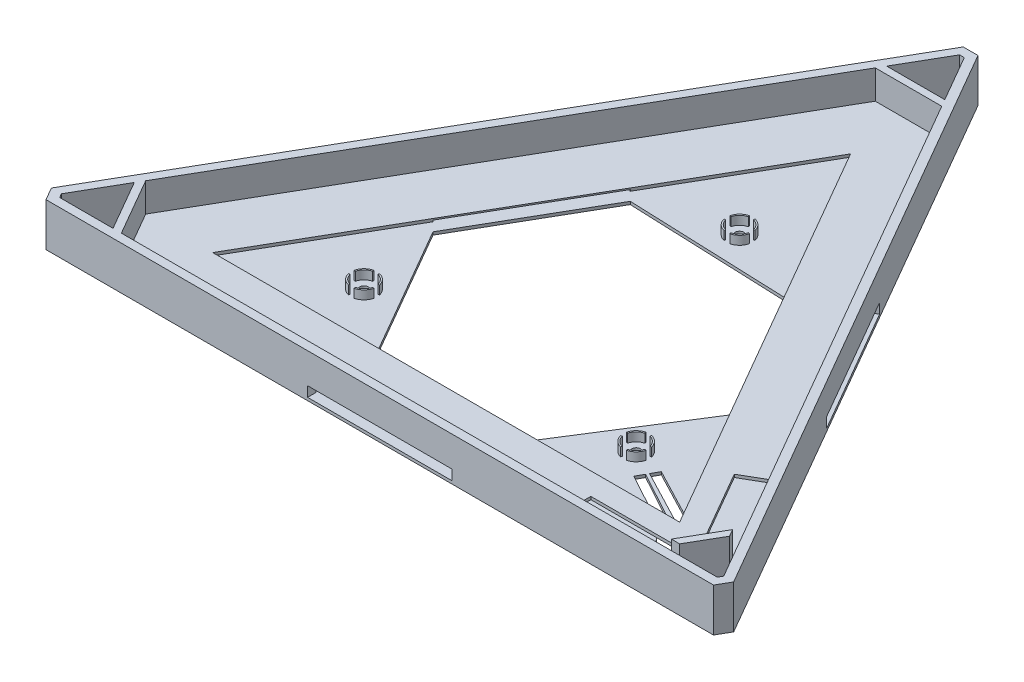
SolidWorks part; units mm, degrees
ref_plane "Front Plane" through (0, 0, 0) normal (0, 0, 1) x (1, 0, 0)
ref_plane "Top Plane" through (0, 0, 0) normal (0, 1, 0) x (1, 0, 0)
ref_plane "Right Plane" through (0, 0, 0) normal (1, 0, 0) x (0, 0, -1)
sketch "Sketch1" plane through (0, 0, 0) normal (0, 1, 0) x (1, 0, 0)
  line L0 (351.2729, 67.6655) -> (468.273, -134.9846)
  line L1 (347.2728, 67.6655) -> (347.2728, 65.1655) construction
  line L2 (409.773, -33.6595) -> (407.6079, -34.9095) construction
  line L3 (468.273, -134.9846) -> (464.2732, -141.9124)
  line L4 (230.2733, -141.9124) -> (464.2732, -141.9124)
  line L5 (230.2733, -141.9124) -> (226.2727, -134.9842)
  line L6 (226.2727, -134.9842) -> (343.2728, 67.6655)
  line L7 (353.4142, 63.9567) -> (351.2491, 62.7067) construction
  line L8 (347.2733, -141.9124) -> (347.2733, -139.4124) construction
  line L9 (231.7167, -139.4124) -> (462.8299, -139.4124)
  line L10 (284.7727, -33.6594) -> (286.9378, -34.9094) construction
  line L11 (344.7161, 65.1655) -> (349.8295, 65.1655)
  line L12 (465.3862, -134.9846) -> (349.8295, 65.1655)
  line L13 (466.2731, -138.4485) -> (464.1081, -137.1985) construction
  line L14 (462.8299, -139.4124) -> (465.3862, -134.9846)
  line L15 (229.1594, -134.9842) -> (344.7161, 65.1655)
  line L16 (229.1594, -134.9842) -> (231.7167, -139.4124)
  line L17 (286.9378, -34.9094) -> (287.3708, -35.1594) construction
  line L18 (230.438, -137.1983) -> (230.871, -136.9483) construction
  line L19 (232.0053, -138.9123) -> (229.7368, -134.9842)
  line L20 (343.2728, 67.6655) -> (351.2729, 67.6655)
  line L21 (345.0048, 64.6655) -> (229.7368, -134.9842)
  line L22 (349.5409, 64.6655) -> (345.0048, 64.6655)
  line L23 (249.0568, -126.4468) -> (246.8918, -127.697) construction
  line L24 (407.6079, -34.9095) -> (407.1749, -35.1595) construction
  line L26 (233.4463, -136.4089) -> (251.9226, -136.4093)
  line L27 (464.8089, -134.9846) -> (462.5412, -138.9123)
  line L28 (462.5412, -138.9123) -> (232.0053, -138.9123)
  line L29 (251.9226, -136.4093) -> (241.8609, -118.9847)
  line L30 (241.8609, -118.9847) -> (232.6236, -134.9842)
  line L31 (232.6236, -134.9842) -> (233.4463, -136.4089)
  line L33 (287.3708, -35.1594) -> (289.5359, -36.4094) construction
  line L34 (254.8093, -136.4089) -> (243.3042, -116.4848)
  line L35 (335.7675, 43.666) -> (243.3042, -116.4848)
  line L36 (358.7782, 43.666) -> (335.7675, 43.666)
  line L38 (289.5359, -36.4094) -> (306.8564, -46.4094) construction
  line L41 (461.939, -134.9846) -> (461.1164, -136.4093)
  line L42 (347.2688, -136.4172) -> (347.2688, -116.4172) construction
  line L43 (442.6021, -136.4093) -> (452.6999, -118.9847)
  line L44 (245.2636, -119.878) -> (249.0568, -126.4468) construction
  line L45 (452.6999, -118.9847) -> (461.939, -134.9846)
  line L48 (461.1164, -136.4093) -> (442.6021, -136.4093)
  line L49 (405.0134, -36.4027) -> (387.6936, -46.404) construction
  line L50 (306.8564, -46.4094) -> (466.2731, -138.4485) construction
  line L51 (357.3348, 46.166) -> (337.2109, 46.166)
  line L52 (337.2109, 46.166) -> (346.4484, 62.1659)
  line L53 (346.4484, 62.1659) -> (348.0966, 62.164)
  line L54 (348.0966, 62.164) -> (357.3348, 46.166)
  line L55 (228.273, -138.4483) -> (387.6936, -46.404) construction
  line L56 (347.2688, -116.4172) -> (347.2728, 43.666) construction
  line L57 (266.4391, -116.428) -> (428.1137, -116.4172)
  line L58 (347.2736, 23.6092) -> (428.1137, -116.4172)
  line L59 (266.4391, -116.428) -> (347.2736, 23.6092)
  line L60 (439.7283, -136.4254) -> (439.7283, -132.9254) construction
  line L61 (451.2487, -116.4715) -> (448.6507, -117.9717) construction
  line L62 (452.6999, -118.9847) -> (358.7782, 43.666)
  line L63 (442.6021, -136.4093) -> (254.8093, -136.4089)
  line L64 (441.749, -132.9254) -> (444.621, -132.9254)
  line L65 (448.6507, -117.9717) -> (450.9647, -121.979) construction
  line L66 (449.5167, -119.4714) -> (450.9647, -121.979)
  line L67 (441.749, -132.9254) -> (449.5167, -119.4714)
  line L68 (450.9647, -121.979) -> (444.621, -132.9254)
  line L69 (461.939, -134.9846) -> (427.2809, -114.9747) construction
  line L70 (461.1164, -136.4093) -> (426.4891, -116.4173) construction
  line L73 (405.0134, -134.9846) -> (439.7283, -134.9846)
  line L74 (405.0134, -134.9846) -> (405.0134, -124.0609)
  line L75 (405.0134, -124.0609) -> (439.7283, -124.0609)
  line L76 (439.7283, -134.9846) -> (439.7283, -124.0609)
  line L77 (405.0134, -124.0609) -> (430.3202, -80.2282) construction
  line L78 (405.0134, -134.9846) -> (433.4739, -85.6896) construction
  line L79 (461.1164, -136.4093) -> (424.3464, -72.7321) construction
  line L80 (432.6513, -87.1143) -> (423.1904, -92.5775)
  line L81 (432.6513, -87.1143) -> (450.1194, -117.365)
  line L82 (423.1904, -92.5775) -> (440.6585, -122.8281)
  line L83 (450.1194, -117.365) -> (440.6585, -122.8281)
  point P13 (407.6079, -34.9095)
  point P20 (464.1081, -137.1985)
  point P23 (347.2733, -139.4124)
  point P25 (347.2732, -141.9124)
  point P27 (347.2728, 65.1655)
  point P31 (286.9378, -34.9094)
  point P37 (287.3708, -35.1594)
  point P39 (230.871, -136.9483)
  point P41 (347.2728, 64.6655)
  point P45 (407.1749, -35.1595)
  point P50 (246.8918, -127.697)
  point P56 (289.5359, -36.4094)
  point P58 (249.0568, -126.4468)
  point P60 (347.2728, 43.666)
  point P62 (345.0048, -136.4089)
  point P64 (445.4885, -126.4485)
  point P71 (447.651, -127.697)
  point P77 (347.2728, 46.166)
  point P84 (347.2688, -116.4172)
  point P87 (387.6936, -46.404)
  point P89 (306.8564, -46.4094)
  point P100 (405.0134, -36.4027)
  dimension "D1" = 2.5
  dimension "D2" = 2.5
  dimension "D3" = 2.5
  dimension "D4" = 2.5
  dimension "D5" = 2.5
  dimension "D6" = 2.5
  dimension "D7" = 0.5
  dimension "D8" = 0.5
  dimension "D9" = 0.5
  dimension "D10" = 2.5
  dimension "D11" = 2.5
  dimension "D12" = 20
  dimension "D13" = 20
  dimension "D14" = 20
  dimension "D15" = 3.5
  dimension "D16" = 3
extrude "Boss-Extrude1" add sketch "Sketch1" along normal blind 1 contours L36 L35 L34 L57 L59 L58 region at (251.4484, 0, 125.0658)
extrude "Boss-Extrude2" add sketch "Sketch1<9>" along normal blind 11 contours L28 L27 L22 L21 L19 L31 L30 L29 L26 L34 L35 L36 L41 L48 L43 L45 L53 L54 L51 L52 | L68 L64 L67 L66 region at (230.7087, 0, 137.042)
sketch "Sketch1<9>" plane through (0, 0, 0) normal (0, 1, 0) x (1, 0, 0) same geometry as "Sketch1"
extrude "Boss-Extrude3" add sketch "Sketch1<10>" along normal blind 5 and the other way blind 3 contours L28 L27 L22 L21 L19 L31 L30 L29 L26 L34 L35 L36 L41 L48 L43 L45 L53 L54 L51 L52 | L68 L64 L67 L66 region at (230.7087, 0, 137.042)
sketch "Sketch1<10>" plane through (0, 0, 0) normal (0, 1, 0) x (1, 0, 0) same geometry as "Sketch1"
sketch "Sketch3" plane through (290.5896, 0, -167.772) normal (0.866, 0, -0.5) x (-0.5, 0, -0.866)
  line L1 (-261.593, -6.5) -> (-211.593, -6.5)
  line L2 (-261.593, -6.5) -> (-261.593, 0.5)
  line L3 (-261.593, 0.5) -> (-211.593, 0.5)
  line L4 (-211.593, -6.5) -> (-211.593, 0.5)
  line L5 (-261.593, -6.5) -> (-211.593, 0.5) construction
  line L6 (-261.593, 0.5) -> (-211.593, -6.5) construction
  point P0 (-236.593, -3)
  dimension "D1" = 50
  dimension "D2" = 7
extrude "Cut-Extrude3" cut sketch "Sketch3" against normal blind 25
sketch "Sketch5" plane through (0, 0, 139.4124) normal (0, 0, 1) x (1, 0, 0)
  line L0 (231.7167, -3) -> (462.8299, -3) construction
  line L1 (322.2733, -6.5) -> (372.2733, -6.5)
  line L2 (322.2733, -6.5) -> (322.2733, 0.5)
  line L3 (322.2733, 0.5) -> (372.2733, 0.5)
  line L4 (372.2733, -6.5) -> (372.2733, 0.5)
  line L5 (322.2733, -6.5) -> (372.2733, 0.5) construction
  line L6 (322.2733, 0.5) -> (372.2733, -6.5) construction
  point P0 (347.2733, -3)
  dimension "D1" = 50
  dimension "D2" = 7
extrude "Cut-Extrude4" cut sketch "Sketch5" against normal blind 25
sketch "Sketch6" plane through (230.3194, 0, 132.9752) normal (-0.866, 0, -0.5) x (-0.5, 0, 0.866)
  line L0 (2.3199, -3) -> (-228.7932, -3) construction
  line L1 (-138.2367, -6.5) -> (-88.2367, -6.5)
  line L2 (-138.2367, -6.5) -> (-138.2367, 0.5)
  line L3 (-138.2367, 0.5) -> (-88.2367, 0.5)
  line L4 (-88.2367, -6.5) -> (-88.2367, 0.5)
  line L5 (-138.2367, -6.5) -> (-88.2367, 0.5) construction
  line L6 (-138.2367, 0.5) -> (-88.2367, -6.5) construction
  point P0 (-113.2367, -3)
  dimension "D1" = 50
  dimension "D2" = 7
extrude "Cut-Extrude5" cut sketch "Sketch6" against normal blind 25
sketch "Sketch8" plane through (0, -3, 0) normal (0, -1, 0) x (1, 0, 0)
  line L1 (349.8295, -65.1655) -> (465.3862, 134.9846)
  line L2 (465.3862, 134.9846) -> (462.8299, 139.4124)
  line L4 (444.621, 132.9254) -> (450.9647, 121.979)
  line L6 (462.8299, 139.4124) -> (231.7167, 139.4124)
  line L9 (452.6999, 118.9847) -> (461.939, 134.9846)
  line L12 (461.939, 134.9846) -> (461.1164, 136.4093)
  line L15 (450.9647, 121.979) -> (444.621, 132.9254) construction
  line L17 (461.1164, 136.4093) -> (442.6021, 136.4093)
  line L19 (322.2733, 116.4243) -> (294.3582, 68.0611)
  line L20 (294.3582, 68.0611) -> (319.3545, 24.7577)
  line L21 (319.3545, 24.7577) -> (376.4737, 26.9694)
  line L22 (376.4737, 26.9694) -> (401.4727, 70.2712)
  line L23 (401.4727, 70.2712) -> (372.2733, 116.4209)
  line L24 (372.2733, 116.4209) -> (322.2733, 116.4243)
  line L25 (386.873, 93.3461) -> (395.3235, 98.6928) construction
  line L30 (308.3157, 92.2427) -> (299.6549, 97.2417) construction
  line L31 (347.9141, 25.8635) -> (348.3013, 15.8635) construction
  line L37 (231.7167, 139.4124) -> (229.1594, 134.9842)
  line L39 (233.4463, 136.4089) -> (251.9226, 136.4093)
  line L40 (251.9226, 136.4093) -> (241.8609, 118.9847)
  line L41 (241.8609, 118.9847) -> (232.6236, 134.9842)
  line L42 (232.6236, 134.9842) -> (233.4463, 136.4089)
  line L43 (349.8295, -65.1655) -> (344.7161, -65.1655)
  line L44 (344.7161, -65.1655) -> (229.1594, 134.9842)
  line L45 (337.2109, -46.166) -> (357.3348, -46.166)
  line L46 (357.3348, -46.166) -> (348.0966, -62.164)
  line L47 (348.0966, -62.164) -> (346.4484, -62.1659)
  line L48 (346.4484, -62.1659) -> (337.2109, -46.166)
  line L53 (442.6021, 136.4093) -> (439.0196, 136.4093)
  line L54 (439.0196, 136.4093) -> (420.3794, 116.4177)
  line L55 (424.5493, 110.2432) -> (451.8713, 117.5496)
  line L59 (372.2733, 116.4209) -> (428.1137, 116.4172) construction
  line L60 (401.4727, 70.2712) -> (428.1137, 116.4172) construction
  line L61 (451.8713, 117.5496) -> (452.6999, 118.9847)
  line L62 (426.6202, 116.4173) -> (441.749, 132.9254)
  line L63 (441.749, 132.9254) -> (444.621, 132.9254)
  line L65 (427.3476, 115.0902) -> (449.5167, 119.4714)
  line L66 (449.5167, 119.4714) -> (450.9647, 121.979)
  line L67 (449.5167, 119.4714) -> (450.9647, 121.979) construction
  line L68 (441.749, 132.9254) -> (449.5167, 119.4714) construction
  line L70 (403.8523, 103.9378) -> (426.6202, 116.4173)
  line L72 (404.333, 103.0609) -> (427.3476, 115.0902)
  line L74 (442.6021, 136.4093) -> (372.2733, 136.4092) construction
  line L75 (461.939, 134.9846) -> (418.7954, 60.2699) construction
  line L76 (420.3794, 116.4177) -> (402.4104, 106.5685)
  line L77 (402.4104, 106.5685) -> (403.8523, 103.9378)
  line L78 (404.333, 103.0609) -> (405.7749, 100.4301)
  line L79 (405.7749, 100.4301) -> (424.5493, 110.2432)
  line L80 (395.3235, 98.6928) -> (447.7929, 127.4522) construction
  line L81 (395.3235, 98.6928) -> (404.0927, 103.4993) construction
  line L82 (404.0927, 103.4993) -> (404.333, 103.0609) construction
  line L83 (404.0927, 103.4993) -> (403.8523, 103.9378) construction
  line L84 (403.8523, 103.9378) -> (402.4104, 106.5685) construction
  line L85 (404.333, 103.0609) -> (405.7749, 100.4301) construction
  line L86 (402.4104, 106.5685) -> (420.3794, 116.4177) construction
  line L87 (405.7749, 100.4301) -> (424.5493, 110.2432) construction
  line L88 (404.333, 103.0609) -> (427.842, 115.9466) construction
  line L89 (403.8523, 103.9378) -> (426.6202, 116.4173) construction
  line L90 (426.6202, 116.4173) -> (427.3476, 115.0902) construction
  line L91 (420.3794, 116.4177) -> (424.1464, 109.5452) construction
  circle A0 centre (395.3235, 98.6928) radius 1.5
  circle A1 centre (348.3013, 15.8635) radius 1.5
  circle A2 centre (299.6549, 97.2417) radius 1.5
  point P4 (424.5493, 110.2432)
  dimension "D6" = 3
  dimension "D7" = 3
  dimension "D8" = 3
  dimension "D1" = 10
  dimension "D2" = 0.5
  dimension "D3" = 10
  dimension "D4" = 10
  dimension "D5" = 10
  dimension "D9" = 0.5
  dimension "D10" = 3
  dimension "D11" = 3
extrude "Boss-Extrude5" add sketch "Sketch8" along normal blind 1
sketch "Sketch12" plane through (0, -3, 0) normal (0, 1, 0) x (1, 0, 0)
  line L0 (348.3013, -11.8635) -> (348.3013, -11.3635) construction
  line L1 (348.3013, -11.3635) -> (349.2951, -11.4746) construction
  line L2 (349.2951, -11.4746) -> (349.1847, -11.9623)
  line L3 (348.3013, -11.3635) -> (347.3075, -11.4746) construction
  line L4 (347.3075, -11.4746) -> (347.4179, -11.9623)
  line L5 (352.3013, -15.8635) -> (352.8013, -15.8635) construction
  line L6 (344.3013, -15.8635) -> (343.8013, -15.8635) construction
  line L7 (348.3013, -19.8635) -> (348.3013, -20.3635) construction
  line L8 (352.8013, -15.8635) -> (352.6902, -14.8697) construction
  line L9 (352.8013, -15.8635) -> (352.6902, -16.8573) construction
  line L10 (343.8013, -15.8635) -> (343.9124, -14.8697) construction
  line L11 (343.8013, -15.8635) -> (343.9124, -16.8573) construction
  line L12 (348.3013, -20.3635) -> (349.2951, -20.2524) construction
  line L13 (348.3013, -20.3635) -> (347.3075, -20.2524) construction
  line L14 (343.9124, -14.8697) -> (348.3013, -15.8635) construction
  line L15 (348.3013, -15.8635) -> (352.6902, -14.8697) construction
  line L16 (343.9124, -16.8573) -> (348.3013, -15.8635) construction
  line L17 (348.3013, -15.8635) -> (352.6902, -16.8573) construction
  line L18 (347.3075, -20.2524) -> (348.3013, -15.8635) construction
  line L19 (348.3013, -15.8635) -> (349.2951, -20.2524) construction
  line L20 (343.9124, -14.8697) -> (344.4001, -14.9801)
  line L21 (343.9124, -16.8573) -> (344.4001, -16.7469)
  line L22 (347.3075, -20.2524) -> (347.4179, -19.7648)
  line L23 (349.2951, -20.2524) -> (349.1847, -19.7648)
  line L24 (352.6902, -14.8697) -> (352.2025, -14.9801)
  line L25 (352.6902, -16.8573) -> (352.2025, -16.7469)
  line L26 (395.3235, -94.1928) -> (395.3235, -98.6928) construction
  line L27 (395.3235, -98.6928) -> (390.8235, -98.6928) construction
  line L28 (390.8235, -98.6928) -> (390.9347, -97.699) construction
  line L29 (399.8235, -98.6928) -> (395.3235, -98.6928) construction
  line L30 (395.3235, -98.6928) -> (395.3235, -103.1928) construction
  line L31 (395.3235, -103.1928) -> (396.3173, -103.0817) construction
  line L32 (395.3235, -94.1928) -> (396.3173, -94.3039) construction
  line L33 (395.3235, -94.1928) -> (394.3297, -94.3039) construction
  line L34 (399.7124, -97.699) -> (399.8235, -98.6928) construction
  line L35 (399.8235, -98.6928) -> (399.7124, -99.6866) construction
  line L36 (390.9347, -99.6866) -> (390.8235, -98.6928) construction
  line L37 (394.3297, -103.0817) -> (395.3235, -103.1928) construction
  line L38 (394.3297, -94.3039) -> (395.3235, -98.6928) construction
  line L39 (395.3235, -98.6928) -> (396.3173, -94.3039) construction
  line L40 (390.9347, -99.6866) -> (395.3235, -98.6928) construction
  line L41 (395.3235, -98.6928) -> (390.9347, -97.699) construction
  line L42 (399.7124, -97.699) -> (395.3235, -98.6928) construction
  line L43 (395.3235, -98.6928) -> (399.7124, -99.6866) construction
  line L44 (394.3297, -103.0817) -> (395.3235, -98.6928) construction
  line L45 (395.3235, -98.6928) -> (396.3173, -103.0817) construction
  line L46 (394.3297, -94.3039) -> (394.4402, -94.7916)
  line L47 (396.3173, -94.3039) -> (396.2069, -94.7916)
  line L48 (399.7124, -97.699) -> (399.2248, -97.8094)
  line L49 (399.7124, -99.6866) -> (399.2248, -99.5762)
  line L50 (396.3173, -103.0817) -> (396.2069, -102.5941)
  line L51 (394.3297, -103.0817) -> (394.4402, -102.5941)
  line L52 (390.9347, -99.6866) -> (391.4223, -99.5762)
  line L53 (390.9347, -97.699) -> (391.4248, -97.7985)
  line L54 (299.6549, -92.7417) -> (299.6549, -97.2417) construction
  line L55 (299.6549, -97.2417) -> (304.1549, -97.2417) construction
  line L56 (299.6549, -101.7417) -> (299.6549, -97.2417) construction
  line L57 (299.6549, -97.2417) -> (295.1549, -97.2417) construction
  line L58 (299.6549, -97.2417) -> (298.6611, -92.8528) construction
  line L59 (298.6611, -92.8528) -> (299.6549, -92.7417) construction
  line L60 (299.6549, -92.7417) -> (300.6487, -92.8528) construction
  line L61 (300.6487, -92.8528) -> (299.6549, -97.2417) construction
  line L62 (299.6549, -97.2417) -> (304.0438, -96.2479) construction
  line L63 (304.0438, -96.2479) -> (304.1549, -97.2417) construction
  line L64 (304.1549, -97.2417) -> (304.0438, -98.2355) construction
  line L65 (304.0438, -98.2355) -> (299.6549, -97.2417) construction
  line L66 (299.6549, -97.2417) -> (300.6487, -101.6306) construction
  line L67 (300.6487, -101.6306) -> (299.6549, -101.7417) construction
  line L68 (299.6549, -101.7417) -> (298.6611, -101.6306) construction
  line L69 (298.6611, -101.6306) -> (299.6549, -97.2417) construction
  line L70 (299.6549, -97.2417) -> (295.266, -98.2355) construction
  line L71 (295.266, -98.2355) -> (295.1549, -97.2417) construction
  line L72 (295.1549, -97.2417) -> (295.266, -96.2479) construction
  line L73 (295.266, -96.2479) -> (299.6549, -97.2417) construction
  line L74 (295.266, -96.2479) -> (295.7537, -96.3583)
  line L75 (295.266, -98.2355) -> (295.7537, -98.1251)
  line L76 (298.6611, -101.6306) -> (298.7715, -101.1429)
  line L77 (300.6487, -101.6306) -> (300.5383, -101.1429)
  line L78 (304.0438, -98.2355) -> (303.5561, -98.1251)
  line L79 (304.0438, -96.2479) -> (303.5561, -96.3583)
  line L80 (300.6487, -92.8528) -> (300.5383, -93.3404)
  line L81 (298.6611, -92.8528) -> (298.7715, -93.3404)
  circle A0 centre (348.3013, -15.8635) radius 4.5
  circle A1 centre (395.3235, -98.6928) radius 4.5
  circle A2 centre (299.6549, -97.2417) radius 4.5
  circle A3 centre (348.3013, -15.8635) radius 4
  circle A4 centre (395.3235, -98.6928) radius 4
  circle A5 centre (299.6549, -97.2417) radius 4
  dimension "D1" = 9
  dimension "D2" = 9
  dimension "D3" = 9
  dimension "D4" = 8
  dimension "D5" = 8
  dimension "D6" = 8
  dimension "D7" = 1
  dimension "D8" = 1
  dimension "D9" = 1
  dimension "D10" = 1
  dimension "D11" = 1
  dimension "D12" = 1
  dimension "D13" = 1
  dimension "D14" = 1
  dimension "D15" = 1
  dimension "D16" = 1
  dimension "D17" = 1
  dimension "D18" = 1
  dimension "D19" = 1
  dimension "D20" = 1
  dimension "D21" = 1
  dimension "D22" = 1
  dimension "D23" = 1
  dimension "D24" = 1
  dimension "D25" = 1
  dimension "D26" = 1
  dimension "D27" = 1
  dimension "D28" = 1
  dimension "D29" = 1
  dimension "D30" = 1
extrude "Boss-Extrude10" add sketch "Sketch12" along normal blind 3 contours A3 L4 A0 L20 | A3 L24 A0 L2 | A3 L23 A0 L25 | A3 L21 A0 L22 | A4 L46 A1 L53 | A4 L48 A1 L47 | A4 L50 A1 L49 | A4 L52 A1 L51 | A5 L81 A2 L74 | A5 L79 A2 L80 | A5 L77 A2 L78 | A5 L75 A2 L76 region at (351.1537, -3, 13.0111) region at (345.4489, -3, 13.0111) region at (351.1537, -3, 18.7159) region at (345.4489, -3, 18.7159) region at (392.4726, -3, 95.8382) region at (398.1759, -3, 95.8404) region at (392.4712, -3, 101.5452) region at (398.1759, -3, 101.5452) region at (296.8025, -3, 94.3893) region at (296.8025, -3, 100.0941) region at (302.5073, -3, 94.3893) region at (302.5073, -3, 100.0941)
